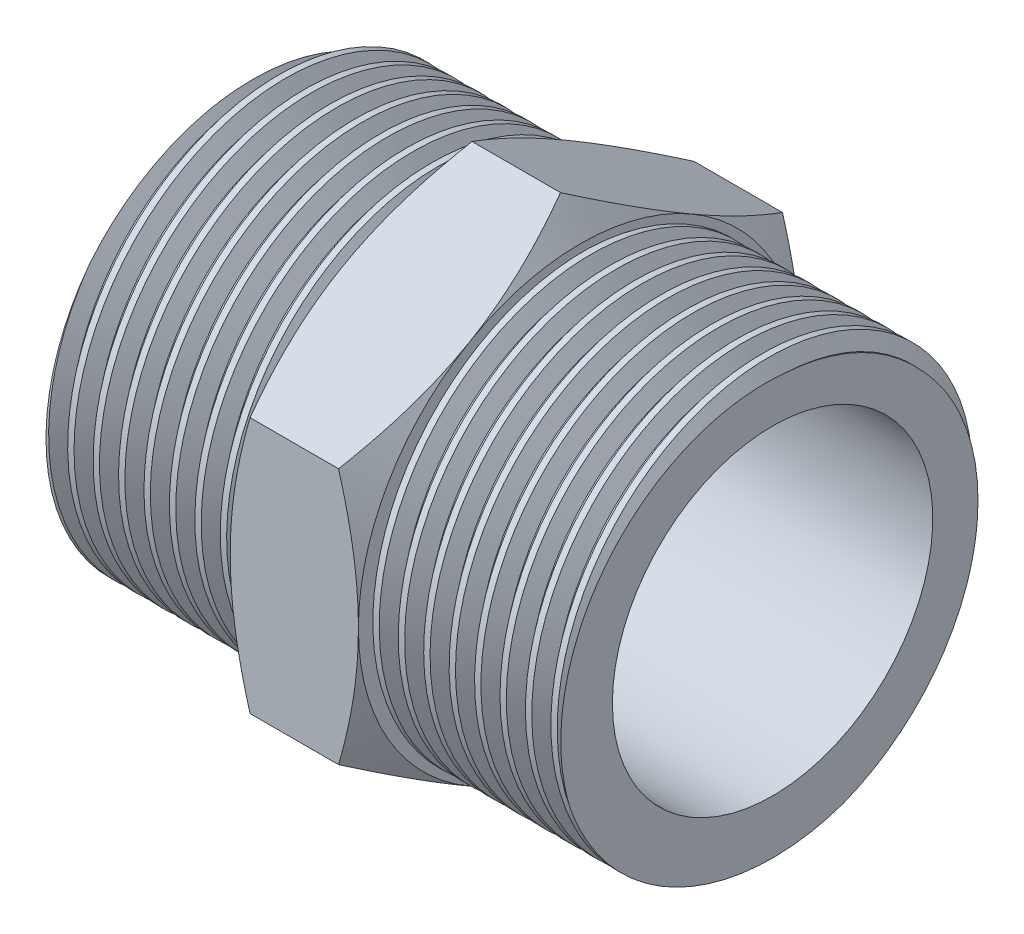
SolidWorks part; units mm, degrees
ref_plane "Front Plane" through (0, 0, 0) normal (0, 0, 1) x (1, 0, 0)
ref_plane "Top Plane" through (0, 0, 0) normal (0, 1, 0) x (1, 0, 0)
ref_plane "Right Plane" through (0, 0, 0) normal (1, 0, 0) x (0, 0, -1)
sketch "Sketch1" plane through (0, 0, 0) normal (0, 0, 1) x (1, 0, 0)
  line L0 (0, 0) -> (4, 0) construction
  line L1 (0, 0) -> (0, 16) construction
  line L2 (4, 16) -> (-9.8564, 8) construction
  line L3 (-9.8564, 8) -> (-9.8564, -8) construction
  line L4 (-9.8564, -8) -> (4, -16) construction
  line L5 (4, -16) -> (17.8564, -8) construction
  line L6 (17.8564, -8) -> (17.8564, 8) construction
  line L7 (17.8564, 8) -> (4, 16) construction
  line L8 (4, 0) -> (4, 22.1973) construction
  line L10 (-13.6235, 10) -> (16, 10) construction
  line L11 (-8.988, 16) -> (9.1362, 16) construction
  line L12 (2.7624, 16) -> (-2.7624, 16)
  line L13 (16, 15) -> (16, 10) construction
  line L16 (16, 10) -> (16, 12.5)
  line L17 (16, 12.5) -> (4, 12.5)
  line L18 (4, 12.5) -> (4, 13.8564)
  line L19 (4, 13.8564) -> (2.7624, 16)
  line L20 (16, 10) -> (-16, 10)
  line L24 (-16, 10) -> (-16, 12.5)
  line L25 (-16, 12.5) -> (-4, 12.5)
  line L26 (-4, 13.8564) -> (-2.7624, 16)
  line L27 (-4, 13.8564) -> (-4, 12.5)
  circle A0 centre (4, 0) radius 13.8564 construction
  point P28 (0, 10)
  dimension "D1" = 4
  dimension "D2" = 2.5
  dimension "D3" = 16
  dimension "D5" = 12.5
  dimension "D6" = 30
  dimension "D8" = 12
revolve "Revolve1" add sketch "Sketch1" angle 360 about L0
sketch "Sketch2" plane through (0, 0, 0) normal (1, 0, 0) x (0, 0, -1)
  line L1 (0, 16) -> (-13.8564, 8)
  line L2 (-13.8564, 8) -> (-13.8564, -8)
  line L3 (-13.8564, -8) -> (0, -16)
  line L4 (0, -16) -> (13.8564, -8)
  line L5 (13.8564, -8) -> (13.8564, 8)
  line L6 (13.8564, 8) -> (0, 16)
  circle A0 centre (0, 0) radius 13.8564 construction
  circle A1 centre (0, 0) radius 16 construction
extrude "Cut-Extrude1" cut sketch "Sketch2" against normal mid plane 10 flip side to cut
thread "Thread1" pitch 1.5875 start angle 0, offset 2, length 0, pitch 1.5875, diameter 25
ref_plane "Plane1" through (18, 0, 12.5) normal (0, 1, 0) x (0, 0, -1)
sketch "Thread Profile1" plane through (18, 0, 12.5) normal (0, 1, 0) x (0, 0, -1)
  line L0 (0, 0) -> (0, 1.5875) construction
  line L11 (0, 0) -> (0, 1.3891)
  line L12 (0, 1.3891) -> (-0.8593, 0.893)
  line L13 (-0.8593, 0.893) -> (-0.8593, 0.4961)
  line L15 (-0.8593, 0.4961) -> (0, 0)
  line L17 (-0.8593, 0.6945) -> (0, 0.6945) construction
  point P2 (0, 0)
  dimension "Pitch" = 1.5875
  dimension "Profile_Angle" = 60
  dimension "Profile_Land" = 0.3969
  dimension "Profile_Height" = 0.8593
sketch "Sketch7" plane through (0, 0, 0) normal (0, 0, 1) x (1, 0, 0)
  line L0 (2.7624, 16) -> (-2.7624, 16) construction
  line L1 (-16, -16) -> (16, -16)
  line L2 (-16, -16) -> (-16, 16)
  line L3 (-16, 16) -> (16, 16)
  line L4 (16, -16) -> (16, 16)
  line L5 (-16, -16) -> (16, 16) construction
  line L6 (-16, 16) -> (16, -16) construction
  point P0 (0, 0)
extrude "Cut-Extrude2" cut sketch "Sketch7" against normal mid plane 40 flip side to cut
